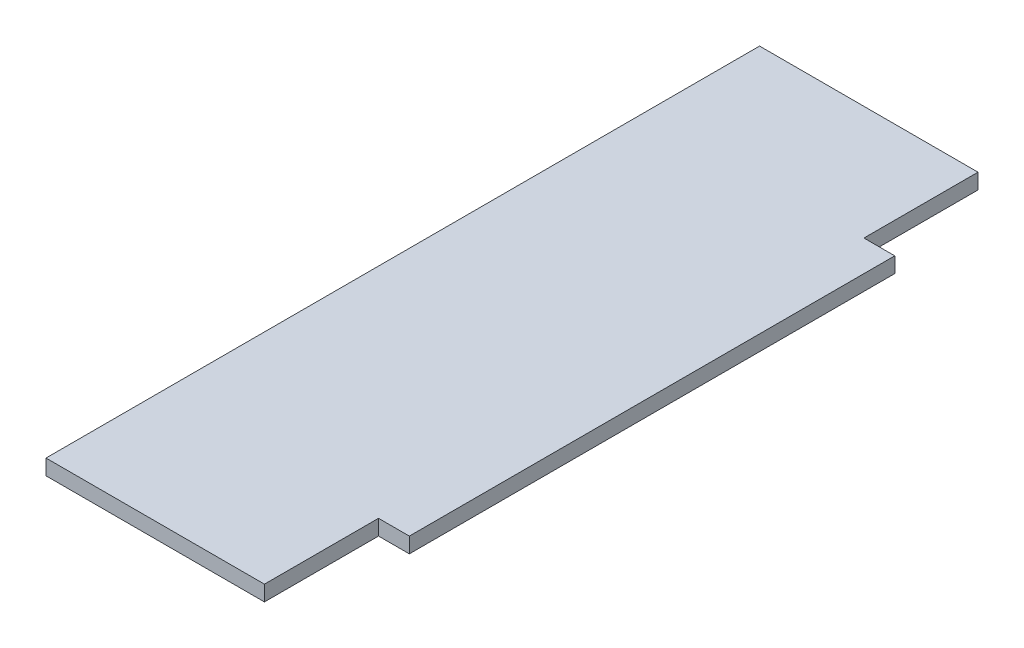
SolidWorks part; units mm, degrees
ref_plane "Front Plane" through (0, 0, 0) normal (0, 0, 1) x (1, 0, 0)
ref_plane "Top Plane" through (0, 0, 0) normal (0, 1, 0) x (1, 0, 0)
ref_plane "Right Plane" through (0, 0, 0) normal (1, 0, 0) x (0, 0, -1)
sketch "Sketch1" plane through (0, 0, 0) normal (0, 1, 0) x (1, 0, 0)
  line L0 (-22.5, 23.5) -> (22.5, 23.5)
  line L1 (22.5, 23.5) -> (22.5, 0)
  line L2 (22.5, 0) -> (28.85, 0)
  line L3 (28.85, 0) -> (28.85, -100)
  line L4 (28.85, -100) -> (22.5, -100)
  line L5 (22.5, -100) -> (22.5, -123.5)
  line L6 (22.5, -123.5) -> (-22.5, -123.5)
  line L7 (-22.5, -123.5) -> (-22.5, -100)
  line L8 (-22.5, -100) -> (-28.85, -100)
  line L9 (-28.85, -100) -> (-28.85, 0)
  line L10 (-28.85, 0) -> (-22.5, 0)
  line L11 (-22.5, 0) -> (-22.5, 23.5)
  line L12 (-22.5, 0) -> (-22.5, -100) construction
  point P11 (0, 23.5)
  point P14 (-28.85, -50)
  dimension "D1" = 6.35
  dimension "D2" = 100
  dimension "D3" = 45
  dimension "D4" = 147
extrude "Boss-Extrude1" add sketch "Sketch1" along normal blind 3.175 contours L11 L12 L7 L6 L5 L4 L3 L2 L1 L0 region at (2.2488, 0, 50)
equation "\"length\" = 147mm"
equation "\"w_mach\"= 45mm"
equation "\"w_tab\"= 100mm"
equation "\"t_wood\"= 0.125in"
equation "\"t_side\"= 0.25in"
equation "\"D1@Sketch1\"=\"t_side\""
equation "\"D2@Sketch1\"=\"w_tab\""
equation "\"D3@Sketch1\"=\"w_mach\""
equation "\"D4@Sketch1\"=\"length\""
equation "\"D1@Boss-Extrude1\"=\"t_wood\""
